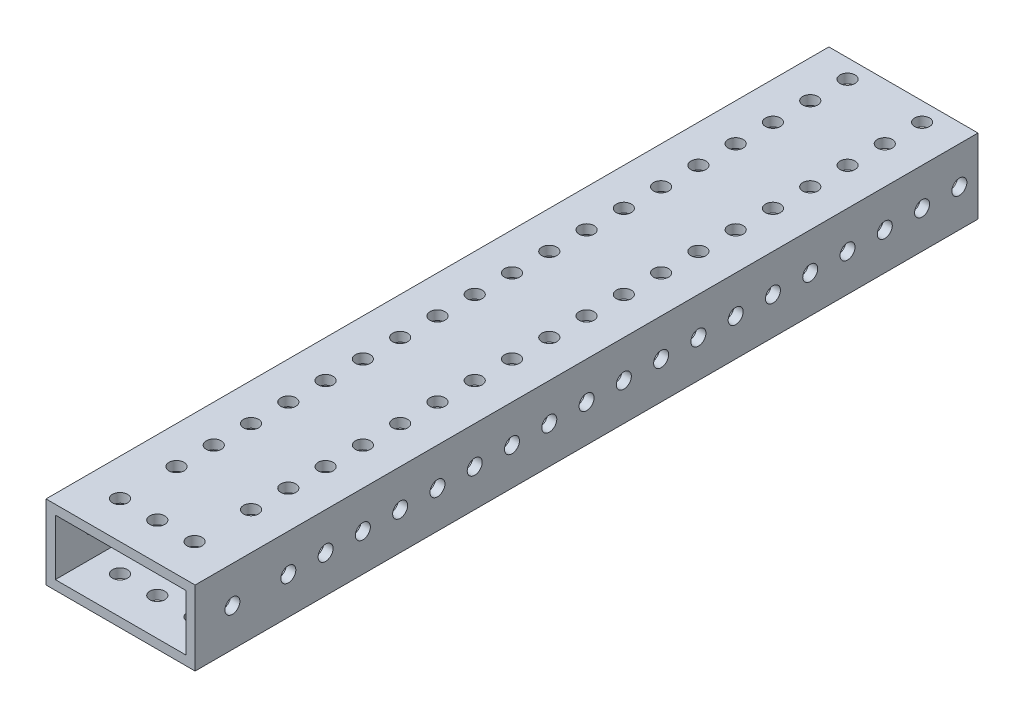
SolidWorks part; units mm, degrees
material "6061-T6 (SS)"
ref_plane "Front Plane" through (0, 0, 0) normal (0, 0, 1) x (1, 0, 0)
ref_plane "Top Plane" through (0, 0, 0) normal (0, 1, 0) x (1, 0, 0)
ref_plane "Right Plane" through (0, 0, 0) normal (1, 0, 0) x (0, 0, -1)
sketch "Sketch1" plane through (0, 0, 0) normal (0, 1, 0) x (1, 0, 0)
  line L1 (0, 0) -> (50.8, 0)
  line L2 (0, 0) -> (0, 266.7)
  line L3 (0, 266.7) -> (50.8, 266.7)
  line L4 (50.8, 0) -> (50.8, 266.7)
  dimension "D1" = 50.8
  dimension "D2" = 266.7
extrude "Boss-Extrude1" add sketch "Sketch1" along normal blind 25.4
sketch "Sketch2" plane through (0, 0, 0) normal (0, 0, 1) x (1, 0, 0)
  line L3 (3.175, 3.175) -> (47.625, 3.175)
  line L4 (3.175, 3.175) -> (3.175, 22.225)
  line L5 (3.175, 22.225) -> (47.625, 22.225)
  line L6 (47.625, 3.175) -> (47.625, 22.225)
  line L7 (0, 25.4) -> (0, 0) construction
  line L8 (50.8, 25.4) -> (50.8, 0) construction
  line L9 (0, 0) -> (50.8, 0) construction
  line L10 (0, 25.4) -> (50.8, 25.4) construction
  point P8 (25.4, 12.7)
  dimension "D1" = 3.175
  dimension "D2" = 3.175
  dimension "D3" = 3.175
  dimension "D4" = 3.175
extrude "Cut-Extrude1" cut sketch "Sketch2" against normal through all
sketch "Sketch4" plane through (0, 25.4, 0) normal (0, 1, 0) x (1, 0, 0)
  line L0 (0, 0) -> (50.8, 0) construction
  line L1 (0, 266.7) -> (0, 0) construction
  line L2 (50.8, 0) -> (50.8, 266.7) construction
  circle A0 centre (12.7, 6.35) radius 2.5527 construction
  circle A1 centre (38.1, 6.35) radius 2.5527 construction
  circle A2 centre (12.7, 19.05) radius 2.5527 construction
  circle A3 centre (38.1, 19.05) radius 2.5527 construction
  circle A4 centre (12.7, 31.75) radius 2.5527
  circle A5 centre (38.1, 31.75) radius 2.5527
  circle A6 centre (12.7, 44.45) radius 2.5527
  circle A7 centre (38.1, 44.45) radius 2.5527
  circle A8 centre (12.7, 57.15) radius 2.5527
  circle A9 centre (38.1, 57.15) radius 2.5527
  circle A10 centre (12.7, 69.85) radius 2.5527
  circle A11 centre (38.1, 69.85) radius 2.5527
  circle A12 centre (12.7, 82.55) radius 2.5527
  circle A13 centre (38.1, 82.55) radius 2.5527
  circle A14 centre (12.7, 95.25) radius 2.5527
  circle A15 centre (38.1, 95.25) radius 2.5527
  circle A16 centre (12.7, 107.95) radius 2.5527
  circle A17 centre (38.1, 107.95) radius 2.5527
  circle A18 centre (12.7, 120.65) radius 2.5527
  circle A19 centre (38.1, 120.65) radius 2.5527
  circle A20 centre (12.7, 133.35) radius 2.5527
  circle A21 centre (38.1, 133.35) radius 2.5527
  circle A22 centre (12.7, 146.05) radius 2.5527
  circle A23 centre (38.1, 146.05) radius 2.5527
  circle A24 centre (12.7, 158.75) radius 2.5527
  circle A25 centre (38.1, 158.75) radius 2.5527
  circle A26 centre (12.7, 171.45) radius 2.5527
  circle A27 centre (38.1, 171.45) radius 2.5527
  circle A28 centre (12.7, 184.15) radius 2.5527
  circle A29 centre (38.1, 184.15) radius 2.5527
  circle A30 centre (12.7, 196.85) radius 2.5527
  circle A31 centre (38.1, 196.85) radius 2.5527
  circle A32 centre (12.7, 209.55) radius 2.5527
  circle A33 centre (38.1, 209.55) radius 2.5527
  circle A34 centre (12.7, 222.25) radius 2.5527
  circle A35 centre (38.1, 222.25) radius 2.5527
  circle A36 centre (12.7, 234.95) radius 2.5527
  circle A37 centre (38.1, 234.95) radius 2.5527
  circle A38 centre (12.7, 247.65) radius 2.5527
  circle A39 centre (38.1, 247.65) radius 2.5527
  circle A40 centre (12.7, 260.35) radius 2.5527
  circle A41 centre (38.1, 260.35) radius 2.5527
  circle A42 centre (12.7, 273.05) radius 2.5527
  circle A43 centre (38.1, 273.05) radius 2.5527
  circle A44 centre (12.7, 285.75) radius 2.5527
  circle A45 centre (38.1, 285.75) radius 2.5527
  circle A46 centre (12.7, 298.45) radius 2.5527
  circle A47 centre (38.1, 298.45) radius 2.5527
  circle A48 centre (12.7, 311.15) radius 2.5527
  circle A49 centre (38.1, 311.15) radius 2.5527
  circle A50 centre (12.7, 323.85) radius 2.5527
  circle A51 centre (38.1, 323.85) radius 2.5527
  circle A52 centre (12.7, 336.55) radius 2.5527
  circle A53 centre (38.1, 336.55) radius 2.5527
  circle A54 centre (12.7, 349.25) radius 2.5527
  circle A55 centre (38.1, 349.25) radius 2.5527
  circle A56 centre (12.7, 361.95) radius 2.5527
  circle A57 centre (38.1, 361.95) radius 2.5527
  circle A58 centre (12.7, 374.65) radius 2.5527
  circle A59 centre (38.1, 374.65) radius 2.5527
  circle A60 centre (12.7, 387.35) radius 2.5527
  circle A61 centre (38.1, 387.35) radius 2.5527
  circle A62 centre (12.7, 400.05) radius 2.5527
  circle A63 centre (38.1, 400.05) radius 2.5527
  circle A64 centre (12.7, 412.75) radius 2.5527
  circle A65 centre (38.1, 412.75) radius 2.5527
  circle A66 centre (12.7, 425.45) radius 2.5527
  circle A67 centre (38.1, 425.45) radius 2.5527
  circle A68 centre (12.7, 438.15) radius 2.5527
  circle A69 centre (38.1, 438.15) radius 2.5527
  circle A70 centre (12.7, 450.85) radius 2.5527
  circle A71 centre (38.1, 450.85) radius 2.5527
  circle A72 centre (12.7, 463.55) radius 2.5527
  circle A73 centre (38.1, 463.55) radius 2.5527
  circle A74 centre (12.7, 476.25) radius 2.5527
  circle A75 centre (38.1, 476.25) radius 2.5527
  circle A76 centre (12.7, 488.95) radius 2.5527
  circle A77 centre (38.1, 488.95) radius 2.5527
  circle A78 centre (12.7, 501.65) radius 2.5527
  circle A79 centre (38.1, 501.65) radius 2.5527
  circle A81 centre (12.5095, 12.7) radius 2.5527
  circle A82 centre (25.2095, 12.7) radius 2.5527
  circle A84 centre (37.9095, 12.7) radius 2.5527
  dimension "D1" = 6.35
  dimension "D2" = 6.35
  dimension "D3" = 5.1054
  dimension "D4" = 5.1054
  dimension "D5" = 12.7
  dimension "D6" = 12.7
  dimension "D8" = 12.7
  dimension "D9" = 5.1054
  dimension "D10" = 12.5095
  dimension "D11" = 12.7
  dimension "D12" = 5.1054
  dimension "D13" = 12.7
  dimension "D14" = 12.7
  dimension "D15" = 12.7
  dimension "D16" = 5.1054
  dimension "D17" = 12.7
  dimension "D7" = 40
sketch "Sketch5" plane through (0, 0, 0) normal (-1, 0, 0) x (0, 0, 1)
  line L0 (-266.7, 0) -> (0, 0) construction
  line L1 (0, 25.4) -> (0, 0) construction
  line L3 (-116.3974, 0) -> (25.4, 0) construction
  line L4 (25.4, 76.2) -> (25.4, 0) construction
  circle A0 centre (-6.35, 12.7) radius 2.5527 construction
  circle A1 centre (-19.05, 12.7) radius 2.5527 construction
  circle A2 centre (-31.75, 12.7) radius 2.5527
  circle A3 centre (-44.45, 12.7) radius 2.5527
  circle A4 centre (-57.15, 12.7) radius 2.5527
  circle A5 centre (-69.85, 12.7) radius 2.5527
  circle A6 centre (-82.55, 12.7) radius 2.5527
  circle A7 centre (-95.25, 12.7) radius 2.5527
  circle A8 centre (-107.95, 12.7) radius 2.5527
  circle A9 centre (-120.65, 12.7) radius 2.5527
  circle A10 centre (-133.35, 12.7) radius 2.5527
  circle A11 centre (-146.05, 12.7) radius 2.5527
  circle A12 centre (-158.75, 12.7) radius 2.5527
  circle A13 centre (-171.45, 12.7) radius 2.5527
  circle A14 centre (-184.15, 12.7) radius 2.5527
  circle A15 centre (-196.85, 12.7) radius 2.5527
  circle A16 centre (-209.55, 12.7) radius 2.5527
  circle A17 centre (-222.25, 12.7) radius 2.5527
  circle A18 centre (-234.95, 12.7) radius 2.5527
  circle A19 centre (-247.65, 12.7) radius 2.5527
  circle A20 centre (-260.35, 12.7) radius 2.5527
  circle A21 centre (-273.05, 12.7) radius 2.5527 construction
  circle A22 centre (-285.75, 12.7) radius 2.5527
  circle A23 centre (-298.45, 12.7) radius 2.5527
  circle A24 centre (-311.15, 12.7) radius 2.5527
  circle A25 centre (-323.85, 12.7) radius 2.5527
  circle A26 centre (-336.55, 12.7) radius 2.5527
  circle A27 centre (-349.25, 12.7) radius 2.5527
  circle A28 centre (-361.95, 12.7) radius 2.5527
  circle A29 centre (-374.65, 12.7) radius 2.5527
  circle A30 centre (-387.35, 12.7) radius 2.5527
  circle A31 centre (-400.05, 12.7) radius 2.5527
  circle A32 centre (-412.75, 12.7) radius 2.5527
  circle A33 centre (-425.45, 12.7) radius 2.5527
  circle A34 centre (-438.15, 12.7) radius 2.5527
  circle A35 centre (-450.85, 12.7) radius 2.5527
  circle A36 centre (-463.55, 12.7) radius 2.5527
  circle A37 centre (-476.25, 12.7) radius 2.5527
  circle A38 centre (-488.95, 12.7) radius 2.5527
  circle A39 centre (-501.65, 12.7) radius 2.5527
  circle A40 centre (-12.7, 12.954) radius 2.5527
  dimension "D1" = 12.7
  dimension "D2" = 6.35
  dimension "D3" = 5.1054
  dimension "D5" = 12.7
  dimension "D6" = 5.1054
  dimension "D7" = 12.954
  dimension "D8" = 38.1
  dimension "D4" = 40
extrude "Cut-Extrude2" cut sketch "Sketch4" against normal through all
extrude "Cut-Extrude3" cut sketch "Sketch5" against normal through all
